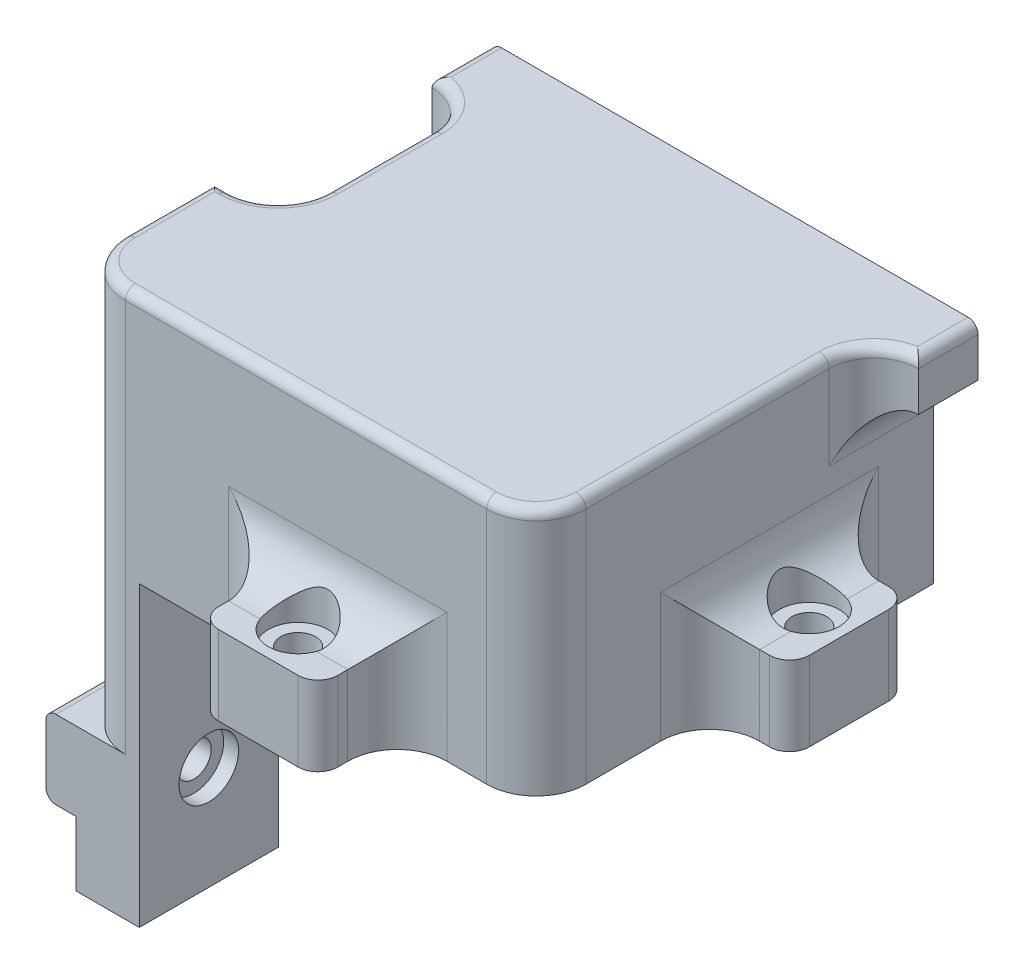
SolidWorks part; units mm, degrees
ref_plane "Alzado" through (0, 0, 0) normal (0, 0, 1) x (1, 0, 0)
ref_plane "Planta" through (0, 0, 0) normal (0, 1, 0) x (1, 0, 0)
ref_plane "Vista lateral" through (0, 0, 0) normal (1, 0, 0) x (0, 0, -1)
sketch "Croquis1" plane through (0, 0, 0) normal (0, 1, 0) x (1, 0, 0)
  line L1 (0, 0) -> (40, 0)
  line L2 (0, 0) -> (0, -40)
  line L3 (0, -40) -> (40, -40)
  line L4 (40, 0) -> (40, -40)
  dimension "D1" = 40
  dimension "D2" = 40
extrude "Saliente-Extruir1" add sketch "Croquis1" along normal blind 25
sketch "Croquis3" plane through (0, 0, 0) normal (0, 0, -1) x (-1, 0, 0)
  line L0 (0, 0) -> (-40, 25) construction
  line L1 (-40, 25) -> (0, 25) construction
  line L2 (-40, 25) -> (-40, 0) construction
  line L4 (-5, 21.5) -> (-35, 21.5)
  line L5 (-5, 21.5) -> (-5, 3.5)
  line L6 (-5, 3.5) -> (-35, 3.5)
  line L7 (-35, 21.5) -> (-35, 3.5)
  line L8 (-5, 21.5) -> (-35, 3.5) construction
  line L9 (-5, 3.5) -> (-35, 21.5) construction
  point P7 (-20, 12.5)
  dimension "D1" = 30
  dimension "D2" = 18
extrude "Cortar-Extruir1" cut sketch "Croquis3" against normal blind 30
sketch "Croquis4" plane through (0, 25, 0) normal (0, 1, 0) x (1, 0, 0)
  line L0 (40, -40) -> (40, 0) construction
  line L1 (35.5, 4) -> (44.5, 4)
  line L2 (35.5, 4) -> (35.5, -6)
  line L3 (35.5, -6) -> (44.5, -6)
  line L4 (44.5, 4) -> (44.5, -6)
  line L5 (4.5, 4) -> (-4.5, 4)
  line L6 (4.5, 4) -> (4.5, -6)
  line L7 (4.5, -6) -> (-4.5, -6)
  line L8 (-4.5, 4) -> (-4.5, -6)
  line L9 (40, 0) -> (0, 0) construction
  line L10 (0, 0) -> (0, -40) construction
  dimension "D1" = 9
  dimension "D2" = 4.5
  dimension "D3" = 10
  dimension "D4" = 4
  dimension "D5" = 9
  dimension "D6" = 10
  dimension "D7" = 4.5
  dimension "D8" = 4
extrude "Saliente-Extruir2" add sketch "Croquis4" against normal blind 5
fillet "Redondeo3" radius 4.5 4 edges at (0, 22.5, 6) (40, 22.5, 6) (0, 20, 3) (40, 20, 3)
sketch "Croquis6" plane through (0, 25, 0) normal (0, 1, 0) x (1, 0, 0)
  line L1 (0, -40) -> (-6.4, -40)
  line L2 (0, -40) -> (0, -26)
  line L3 (0, -26) -> (-6.4, -26)
  line L4 (-6.4, -40) -> (-6.4, -26)
  dimension "D1" = 6.4
  dimension "D2" = 14
extrude "Saliente-Extruir3" add sketch "Croquis6" against normal blind 55
sketch "Croquis7" plane through (-6.4, 0, 0) normal (-1, 0, 0) x (0, 0, 1)
  line L0 (33, -30) -> (33, 25) construction
  line L1 (26, -30) -> (40, -30) construction
  line L2 (26, 25) -> (40, 25) construction
  line L3 (26, -30) -> (26, 25) construction
  line L4 (26, -23.5) -> (40, -23.5)
  line L5 (26, -23.5) -> (26, -15.6)
  line L6 (26, -15.6) -> (40, -15.6)
  line L7 (40, -23.5) -> (40, -15.6)
  line L8 (40, -30) -> (40, 25) construction
  dimension "D1" = 7.9
  dimension "D2" = 6.5
extrude "Saliente-Extruir4" add sketch "Croquis7" along normal blind 3
sketch "Croquis8" plane through (-9.4, 0, 0) normal (-1, 0, 0) x (0, 0, 1)
  line L0 (33, -23.5) -> (33, -15.6) construction
  line L1 (26, -23.5) -> (40, -23.5) construction
  line L2 (40, -15.6) -> (26, -15.6) construction
  circle A0 centre (33, -19.55) radius 1.75
  dimension "D1" = 3.5
extrude "Cortar-Extruir2" cut sketch "Croquis8" against normal up to surface (9.4 mm away) up to face at (0, -15, 33)
sketch "Croquis9" plane through (0, 0, 0) normal (1, 0, 0) x (0, 0, -1)
  circle A0 centre (-33, -19.55) radius 3
  dimension "D1" = 6
extrude "Cortar-Extruir3" cut sketch "Croquis9" against normal blind 1.5
fillet "Redondeo4" radius 1 2 edges at (-9.4, -15.6, 33) (-9.4, -23.5, 33)
sketch "Croquis10" plane through (0, 0, 0) normal (0, -1, 0) x (1, 0, 0)
  line L0 (0, 40) -> (40, 40) construction
  line L1 (40, 10.5) -> (48, 10.5)
  line L2 (40, 10.5) -> (40, 22.5)
  line L3 (40, 22.5) -> (48, 22.5)
  line L4 (48, 10.5) -> (48, 22.5)
  line L5 (26, 40) -> (14, 40)
  line L6 (26, 40) -> (26, 48)
  line L7 (26, 48) -> (14, 48)
  line L8 (14, 40) -> (14, 48)
  line L9 (20, 0) -> (20, 40) construction
  line L10 (40, 0) -> (0, 0) construction
  dimension "D1" = 8
  dimension "D2" = 12
  dimension "D3" = 12
  dimension "D4" = 8
  dimension "D5" = 6
extrude "Saliente-Extruir5" add sketch "Croquis10" against normal blind 8
sketch "Croquis11" plane through (0, 0, 0) normal (0, -1, 0) x (1, 0, 0)
  line L0 (48, 16.5) -> (39.123, 16.5) construction
  line L1 (48, 10.5) -> (48, 22.5) construction
  line L2 (20, 48) -> (20, 38.3926) construction
  line L3 (26, 48) -> (14, 48) construction
  line L4 (44, 10.5) -> (44, 22.5) construction
  line L5 (40, 10.5) -> (48, 10.5) construction
  line L6 (48, 22.5) -> (40, 22.5) construction
  line L7 (26, 44) -> (14, 44) construction
  line L8 (26, 40) -> (26, 48) construction
  line L9 (14, 48) -> (14, 40) construction
  circle A0 centre (44, 16.5) radius 1.75
  circle A1 centre (20, 44) radius 1.75
  dimension "D1" = 3.5
  dimension "D2" = 3.5
extrude "Cortar-Extruir4" cut sketch "Croquis11" against normal up to surface (8 mm away) up to face at (44, 8, 16.5)
sketch "Croquis12" plane through (0, 8, 0) normal (0, 1, 0) x (1, 0, 0)
  circle A0 centre (44, -16.5) radius 3
  circle A1 centre (20, -44) radius 3
  dimension "D1" = 6
  dimension "D2" = 6
extrude "Cortar-Extruir5" cut sketch "Croquis12" against normal blind 1.5
fillet "Redondeo5" radius 5 9 edges at (0, 12.5, 26) (14, 4, 40) (20, 8, 40) (26, 4, 40) (40, 4, 22.5) (40, 8, 16.5) (40, 4, 10.5) (-6.4, 4.7, 40) (40, 12.5, 40)
fillet "Redondeo6" radius 1 12 edges at (41.318, 25, 7.318) (40, 25, 22.75) (38.5355, 25, 38.5355) (16.8, 25, 40) (-4.9355, 25, 38.5355) (-1.318, 25, 7.318) (-5.7, 25, 26) (-1.4645, 25, 24.5355) (44.5, 25, 1) (-6.4, 25, 30.5) (-4.5, 25, 1) (0, 25, 15.75)
fillet "Redondeo7" radius 2 4 edges at (48, 4, 10.5) (48, 4, 22.5) (14, 4, 48) (26, 4, 48)
sketch "Croquis13" plane through (0, 20, 0) normal (0, -1, 0) x (1, 0, 0)
  line L4 (4.5, 0) -> (-4.5, 0)
  line L5 (-4.5, 0) -> (-4.5, -4)
  line L6 (-4.5, -4) -> (4.5, -4)
  line L7 (4.5, -4) -> (4.5, 0)
  line L8 (4.5, 0) -> (-4.5, 0)
  line L9 (-4.5, 0) -> (-4.5, -4)
  line L10 (-4.5, -4) -> (4.5, -4)
  line L11 (4.5, -4) -> (4.5, 0)
  line L12 (44.5, -4) -> (44.5, 0)
  line L13 (44.5, 0) -> (35.5, 0)
  line L14 (35.5, 0) -> (35.5, -4)
  line L15 (35.5, -4) -> (44.5, -4)
  line L16 (44.5, -4) -> (44.5, 0)
  line L17 (44.5, 0) -> (35.5, 0)
  line L18 (35.5, 0) -> (35.5, -4)
  line L19 (35.5, -4) -> (44.5, -4)
  dimension "D1" = 0
  dimension "D2" = 0
extrude "Cortar-Extruir6" cut sketch "Croquis13" against normal through all
